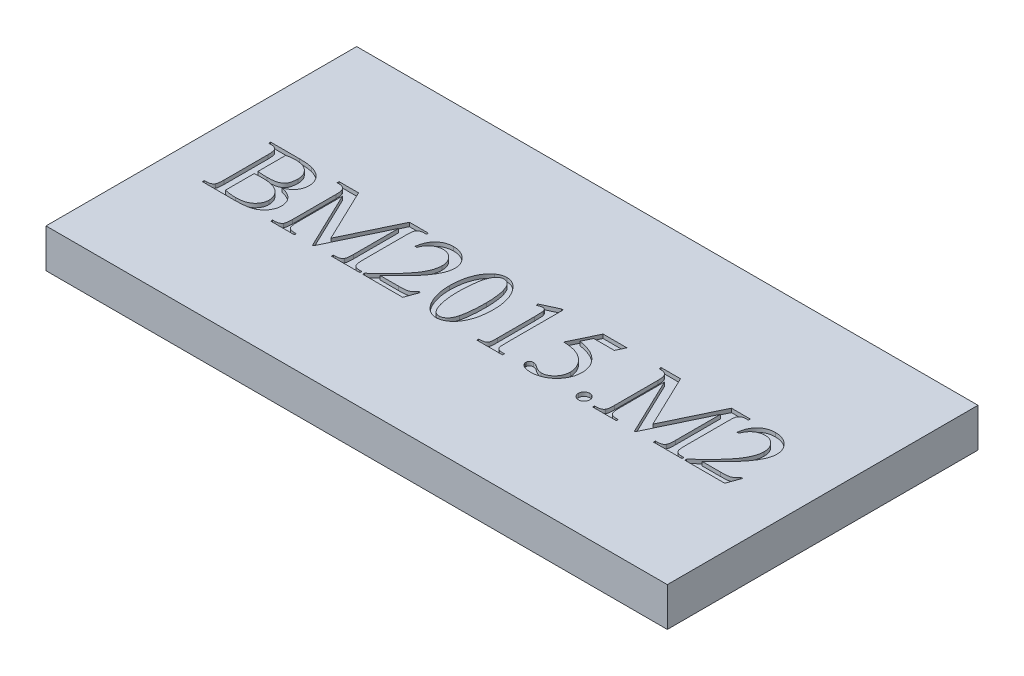
SolidWorks part; units mm, degrees
material "Д16Т ГОСТ 4784-74"
ref_plane "Спереди" through (0, 0, 0) normal (0, 0, 1) x (1, 0, 0)
ref_plane "Сверху" through (0, 0, 0) normal (0, 1, 0) x (1, 0, 0)
ref_plane "Сбоку" through (0, 0, 0) normal (1, 0, 0) x (0, 0, -1)
sketch "Эскиз1" plane through (0, 0, 0) normal (0, 1, 0) x (1, 0, 0)
  line L1 (-80, -40) -> (80, -40)
  line L2 (-80, -40) -> (-80, 40)
  line L3 (-80, 40) -> (80, 40)
  line L4 (80, -40) -> (80, 40)
  line L5 (-80, -40) -> (80, 40) construction
  line L6 (-80, 40) -> (80, -40) construction
  point P0 (0, 0)
  dimension "D1" = 80
  dimension "D2" = 160
extrude "Бобышка-Вытянуть1" add sketch "Эскиз1" along normal blind 10
sketch "Эскиз2" plane through (0, 10, 0) normal (0, 1, 0) x (1, 0, 0)
  line L0 (80, 40) -> (-80, 40) construction
  line L1 (-80, 40) -> (-80, -40) construction
  text T0 "BM2015.M2" font "Times New Roman" height in points 72
  dimension "D1" = 50
  dimension "D2" = 10
extrude "Вырез-Вытянуть1" cut sketch "Эскиз2" against normal blind 1
